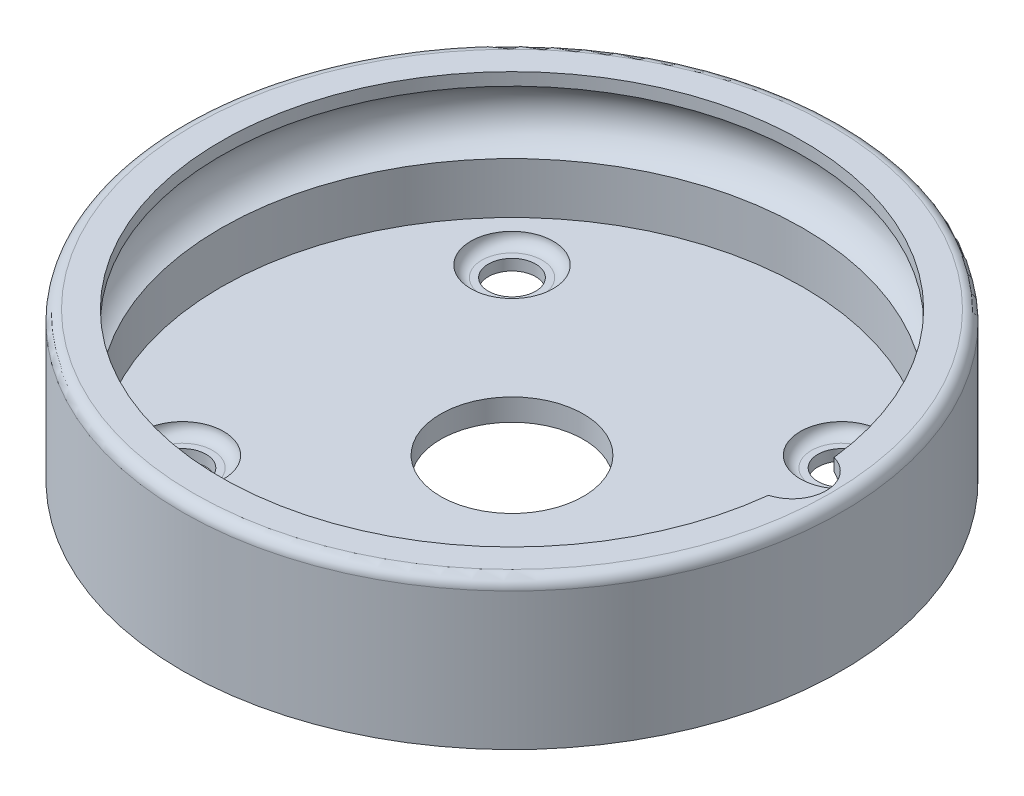
SolidWorks part; units mm, degrees
ref_plane "前视基准面" through (0, 0, 0) normal (0, 0, 1) x (1, 0, 0)
ref_plane "上视基准面" through (0, 0, 0) normal (0, 1, 0) x (1, 0, 0)
ref_plane "右视基准面" through (0, 0, 0) normal (1, 0, 0) x (0, 0, -1)
sketch "草图1" plane through (0, 0, 0) normal (0, 0, 1) x (1, 0, 0)
  line L0 (6.5, 0) -> (30, 0)
  line L1 (30, 0) -> (30, 2)
  line L2 (30, 2) -> (30, 12.5)
  line L3 (29, 13.5) -> (26.5, 13.5)
  line L4 (0, 2) -> (0, 0)
  line L5 (6.5, 2) -> (30, 2)
  line L6 (6.5, 2) -> (6.5, 0)
  line L7 (26.5, 12.5) -> (26.5, 12.3549)
  line L8 (26.5, 6.5) -> (26.5, 2)
  line L9 (26.5, 13.5) -> (26.5, 12.5)
  line L10 (26.5, 6.6451) -> (26.5, 6.5)
  arc A2 (30, 12.5) -> (29, 13.5) centre (29, 12.5) ccw
  arc A3 (26.5, 6.6451) -> (26.5, 12.3549) centre (25.5, 9.5) ccw
  point P12 (30, 13.5)
  point P14 (30, 13.5)
  dimension "D2" = 4
  dimension "D3" = 1
  dimension "D1" = 13.5
  dimension "D4" = 6.5
  dimension "D5" = 23.5
  dimension "D6" = 1
revolve "旋转2" add sketch "草图1" angle 360 about L4 region at (18.25, 1, 0) region at (28.4829, 7.2453, 0)
sketch "草图3" plane through (0, 13.5, 0) normal (0, 1, 0) x (1, 0, 0)
  circle A0 centre (25.5, 0) radius 3.1
  circle A1 centre (0, 0) radius 30 construction
  dimension "D1" = 25.5
extrude "切除-拉伸2" cut sketch "草图3" against normal blind 4
sketch "草图4" plane through (0, 2, 0) normal (0, 1, 0) x (1, 0, 0)
  line L1 (-15, 15) -> (15, 15)
  line L2 (-15, 15) -> (-15, -15)
  line L3 (-15, -15) -> (15, -15)
  line L4 (15, 15) -> (15, -15)
  line L5 (-15, 15) -> (15, -15) construction
  line L6 (-15, -15) -> (15, 15) construction
  circle A0 centre (-15, 15) radius 2.15
  point P0 (0, 0)
  point P6 (0, 0)
  dimension "D1" = 30
extrude "切除-拉伸3" cut sketch "草图4" against normal through all contours L1 A0 L2 | L2 A0 L1 region at (-15.3042, 2, -15.3042) region at (-14.0875, 2, -14.0875)
sketch "草图5" plane through (0, 2, 0) normal (0, 1, 0) x (1, 0, 0)
  circle A0 centre (-15, 15) radius 3.75
extrude "切除-拉伸4" cut sketch "草图5" against normal blind 1
fillet "圆角1" radius 1 1 edges at (-15, 1, -11.25)
ref_axis "基准轴1" through (0, 0, 0) along (0, 1, 0)
pattern_circular "阵列(圆周)1" count 4 every 90 about axis through (0, 0, 0) along (0, 1, 0) of "切除-拉伸3", "切除-拉伸4", "圆角1"
sketch "草图6" plane through (0, 2, 0) normal (0, 1, 0) x (1, 0, 0)
  line L0 (25.5, 0) -> (26.5, 0)
  circle A0 centre (25.5, 0) radius 1
  circle A1 centre (0, 0) radius 26.5 construction
  dimension "D1" = 1
extrude "切除-拉伸5" cut sketch "草图6" against normal through all contours A0 region at (24.5283, 2, 0)
